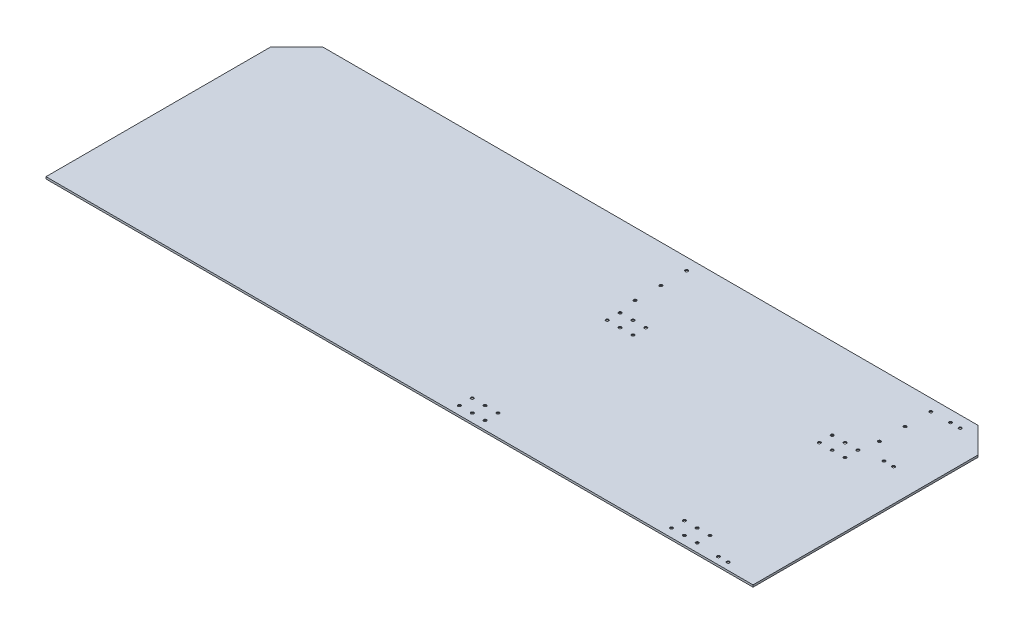
SolidWorks part; units mm, degrees
material "6061-T6 (SS)"
ref_plane "Front Plane" through (0, 0, 0) normal (0, 0, 1) x (1, 0, 0)
ref_plane "Top Plane" through (0, 0, 0) normal (0, 1, 0) x (1, 0, 0)
ref_plane "Right Plane" through (0, 0, 0) normal (1, 0, 0) x (0, 0, -1)
sketch "Sketch1" plane through (0, 0, 0) normal (0, 1, 0) x (1, 0, 0)
  line L1 (-550, -195) -> (550, -195)
  line L2 (-550, -195) -> (-550, 195)
  line L3 (-550, 195) -> (550, 195)
  line L4 (550, -195) -> (550, 195)
  line L5 (-550, -195) -> (550, 195) construction
  line L6 (-550, 195) -> (550, -195) construction
  point P0 (0, 0)
  dimension "D1" = 1100
  dimension "D2" = 390
extrude "Boss-Extrude1" add sketch "Sketch1" along normal blind 3.175
chamfer "Chamfer1" distance 40 angle 45 2 edges at (-550, 1.5875, -195) (550, 1.5875, -195)
hole_wizard "Laptop Support Holes" positions "Sketch12" profile "Sketch13" countersink size "M4" standard "ANSI Metric"
sketch "Sketch12" plane through (0, 0, 0) normal (0, -1, 0) x (-1, 0, 0)
  line L0 (550, -195) -> (-550, -195) construction
  point P0 (-450, -181.825)
  point P11 (-430, -181.825)
  point P12 (-410, -181.825)
  point P13 (-430, -161.825)
  point P14 (-410, -161.825)
  point P15 (-450, -161.825)
  dimension "D1" = 13.175
  dimension "D2" = 100
  dimension "D3" = 3
  dimension "D4" = 2
sketch "Sketch13" plane through (450, 0, 181.825) normal (1, 0, 0) x (0, 0, -1)
  line L0 (0, 0) -> (0, 16.3519)
  line L1 (0, 16.3519) -> (2.25, 15)
  line L2 (2.25, 15) -> (2.25, 2.23)
  line L3 (2.25, 2.23) -> (4.48, 0)
  line L5 (4.48, 0) -> (0, 0)
  line L6 (-2.25, 2.23) -> (-4.48, 0) construction
  line L10 (0, 16.3519) -> (-2.25, 15) construction
  line L11 (0, -6.35) -> (0, 107.95) construction
  dimension "Hole Dia." = 4.5
  dimension "Hole Depth" = 15
  dimension "Near C'Sink Dia." = 8.96
  dimension "Near C'Sink Angle" = 90
  dimension "Drill Angle" = 118
pattern_linear "LPattern1" count 2 spacing 330 along (-1, 0, 0) count 2 spacing 230 along (0, 0, -1) of "Laptop Support Holes"
hole_wizard "Fan Support Holes" positions "Sketch14" profile "Sketch16" countersink size "M4" standard "ANSI Metric" end condition through all
sketch "Sketch14" plane through (0, 0, 0) normal (0, -1, 0) x (-1, 0, 0)
  line L0 (-500, 73.675) -> (-485, 73.675)
  line L2 (-550, -195) -> (-550, 155) construction
  line L3 (550, -195) -> (-550, -195) construction
  line L4 (-500, 177.325) -> (-485, 177.325)
  line L5 (-510, 195) -> (510, 195) construction
  line L6 (-500, -183.825) -> (-485, -183.825)
  point P1 (-500, 73.675)
  point P2 (-485, 73.675)
  point P10 (-500, 177.325)
  point P11 (-485, 177.325)
  point P24 (-500, -183.825)
  point P25 (-485, -183.825)
  point P33 (0, 0)
  point P34 (0, 0)
  dimension "D1" = 15
  dimension "D2" = 50
  dimension "D3" = 257.5
  dimension "D4" = 17.675
  dimension "D5" = 11.175
sketch "Sketch16" plane through (500, 0, -73.675) normal (1, 0, 0) x (0, 0, -1)
  line L0 (0, 0) -> (0, 3.175)
  line L1 (0, 3.175) -> (2.25, 3.175)
  line L2 (2.25, 3.175) -> (2.25, 2.23)
  line L3 (2.25, 2.23) -> (4.48, 0)
  line L5 (4.48, 0) -> (0, 0)
  line L6 (-2.25, 2.23) -> (-4.48, 0) construction
  line L11 (0, -6.35) -> (0, 107.95) construction
  dimension "Thru Hole Dia." = 4.5
  dimension "Thru Hole Depth" = 3.175
  dimension "Near C'Sink Dia." = 8.96
  dimension "Near C'Sink Angle" = 90
hole_wizard "Back Bay Holes" positions "Sketch20" profile "Sketch21" countersink size "M4" standard "ANSI Metric"
sketch "Sketch20" plane through (0, 0, 0) normal (0, -1, 0) x (-1, 0, 0)
  line L0 (-510, 195) -> (510, 195) construction
  point P0 (-455, 176.585)
  point P14 (-455, 136.585)
  point P15 (-455, 96.585)
  dimension "D1" = 18.415
  dimension "D2" = 95
  dimension "D3" = 3
sketch "Sketch21" plane through (455, 0, -176.585) normal (1, 0, 0) x (0, 0, -1)
  line L0 (0, 0) -> (0, 13.3519)
  line L1 (0, 13.3519) -> (2.25, 12)
  line L2 (2.25, 12) -> (2.25, 2.23)
  line L3 (2.25, 2.23) -> (4.48, 0)
  line L5 (4.48, 0) -> (0, 0)
  line L6 (-2.25, 2.23) -> (-4.48, 0) construction
  line L10 (0, 13.3519) -> (-2.25, 12) construction
  line L11 (0, -6.35) -> (0, 107.95) construction
  dimension "Hole Dia." = 4.5
  dimension "Hole Depth" = 12
  dimension "Near C'Sink Dia." = 8.96
  dimension "Near C'Sink Angle" = 90
  dimension "Drill Angle" = 118
pattern_linear "LPattern3" count 2 spacing 380 along (-1, 0, 0) of "Back Bay Holes"
